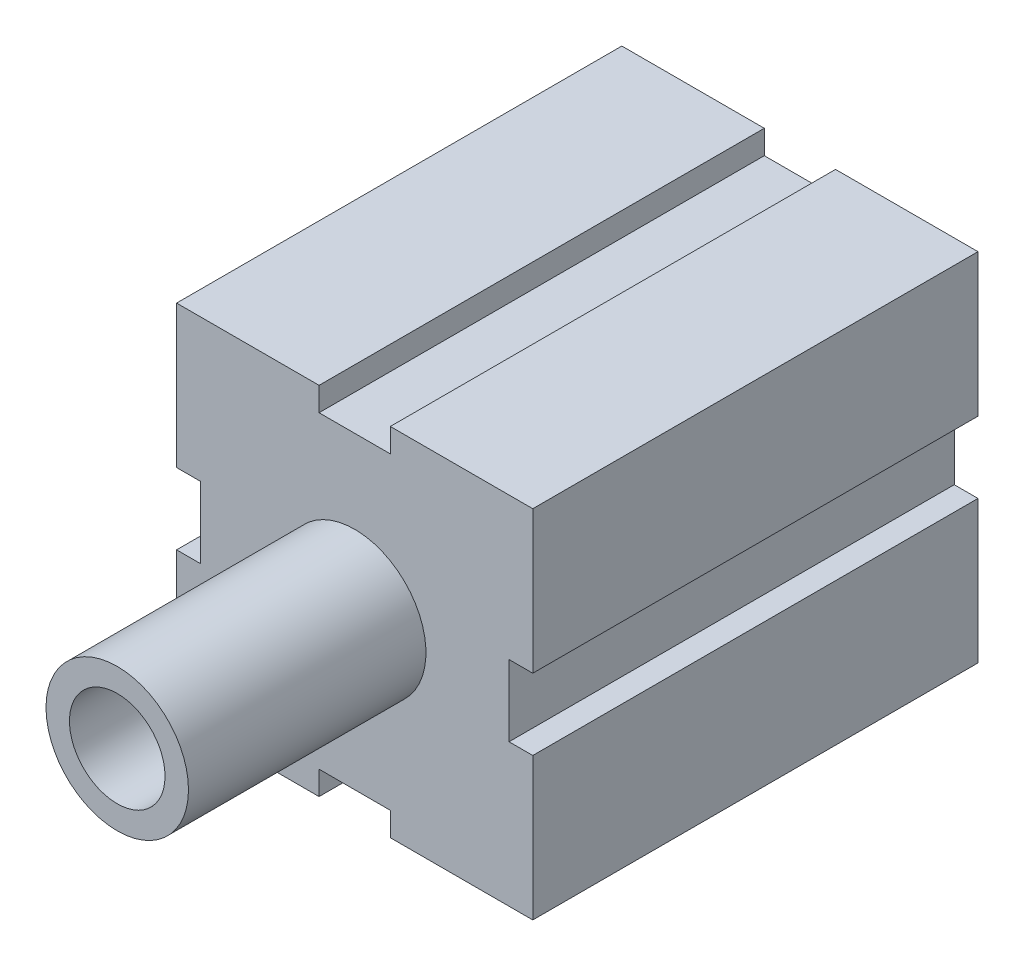
SolidWorks part; units mm, degrees
ref_plane "Front Plane" through (0, 0, 0) normal (0, 0, 1) x (1, 0, 0)
ref_plane "Top Plane" through (0, 0, 0) normal (0, 1, 0) x (1, 0, 0)
ref_plane "Right Plane" through (0, 0, 0) normal (1, 0, 0) x (0, 0, -1)
sketch "Sketch1" plane through (0, 0, 0) normal (0, 0, 1) x (1, 0, 0)
  line L1 (302.8649, 107.5498) -> (332.8649, 107.5498)
  line L2 (302.8649, 107.5498) -> (302.8649, 77.5498)
  line L3 (302.8649, 77.5498) -> (332.8649, 77.5498)
  line L4 (332.8649, 107.5498) -> (332.8649, 77.5498)
  dimension "D1" = 30
  dimension "D2" = 30
extrude "Boss-Extrude1" add sketch "Sketch1" along normal blind 37.5 contours L2 L3 L4 L1
sketch "Sketch2" plane through (0, 0, 37.5) normal (0, 0, 1) x (1, 0, 0)
  line L0 (317.8649, 77.5498) -> (317.8649, 107.5498) construction
  line L1 (302.8649, 77.5498) -> (332.8649, 77.5498) construction
  line L2 (302.8649, 107.5498) -> (332.8649, 107.5498) construction
  circle A0 centre (317.8649, 92.5498) radius 6
  circle A1 centre (317.8649, 92.5498) radius 4.025
extrude "Boss-Extrude2" add sketch "Sketch2" along normal blind 20
sketch "Sketch3" plane through (0, 0, 37.5) normal (0, 0, 1) x (1, 0, 0)
  circle A0 centre (317.8649, 92.5498) radius 4.025
extrude "Cut-Extrude1" cut sketch "Sketch3" against normal blind 20
sketch "Sketch4" plane through (0, 77.5498, 0) normal (0, -1, 0) x (1, 0, 0)
  line L0 (302.8649, 0) -> (332.8649, 0) construction
  line L1 (314.8649, -37.5) -> (320.8649, -37.5)
  line L2 (314.8649, -37.5) -> (314.8649, 37.5)
  line L3 (314.8649, 37.5) -> (320.8649, 37.5)
  line L4 (320.8649, -37.5) -> (320.8649, 37.5)
  line L5 (314.8649, -37.5) -> (320.8649, 37.5) construction
  line L6 (314.8649, 37.5) -> (320.8649, -37.5) construction
  line L7 (302.8649, 37.5) -> (332.8649, 37.5) construction
  point P0 (317.8649, 0)
  dimension "D1" = 6
extrude "Cut-Extrude2" cut sketch "Sketch4" against normal blind 2
pattern_circular "CirPattern1" count 4 every 90 about axis through (317.8649, 92.5498, 17.5) along (0, 0, 1) of "Cut-Extrude2"
